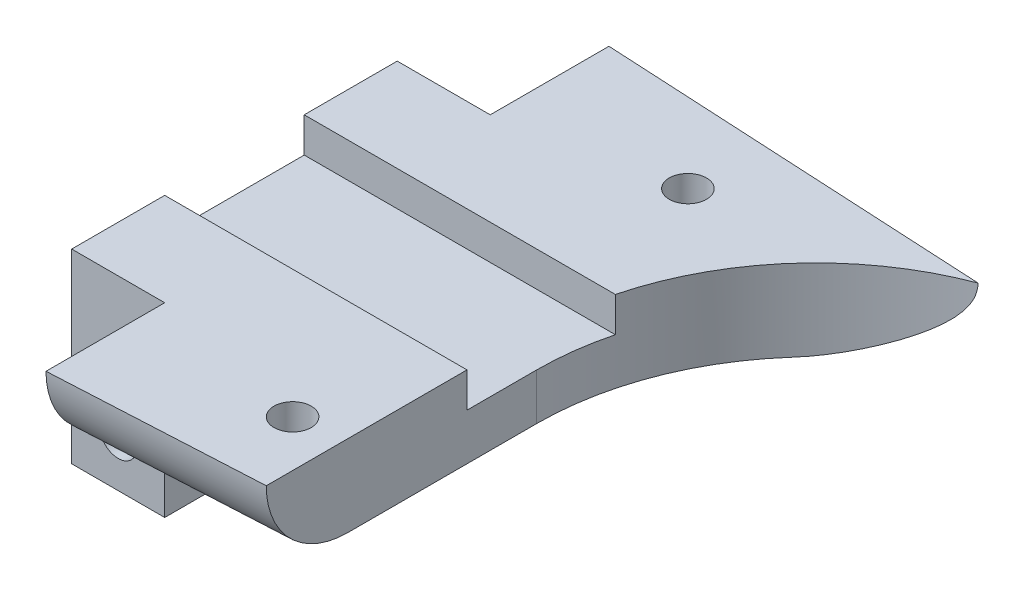
SolidWorks part; units mm, degrees
ref_plane "Front" through (0, 0, 0) normal (0, 0, 1) x (1, 0, 0)
ref_plane "Top" through (0, 0, 0) normal (0, 1, 0) x (1, 0, 0)
ref_plane "Right" through (0, 0, 0) normal (1, 0, 0) x (0, 0, -1)
sketch "Sketch1" plane through (0, 0, 0) normal (0, 1, 0) x (1, 0, 0)
  line L0 (0, 0) -> (38, 0) construction
  line L2 (0, 13) -> (17, 12.1053) construction
  line L3 (17, -12.1053) -> (33.7535, -11.2235)
  line L4 (0, -13) -> (17, -12.1053) construction
  line L5 (13, 0) -> (13, 7)
  line L7 (26, 0) -> (26, -11.6316)
  line L8 (17, 10) -> (17, 12.1053)
  line L9 (17, 12.1053) -> (33.7535, 11.2235)
  line L10 (17, -10) -> (17, -12.1053)
  line L13 (13, 7) -> (17, 7)
  line L14 (17, 7) -> (17, 10)
  line L15 (13, 0) -> (13, -7)
  line L16 (13, -7) -> (17, -7)
  line L17 (17, -7) -> (17, -10)
  circle A0 centre (0, 0) radius 13
  circle A1 centre (38, 0) radius 12
extrude "Boss-Extrude1" add sketch "Sketch1" against normal blind 3.5 contours A1 L9 L8 L14 L13 L5 L15 L16 L17 L10 L3 L7 region at (20.8147, 0, -0.7569)
sketch "Sketch2" plane through (0, 0, 0) normal (0, 1, 0) x (1, 0, 0)
  line L0 (0, 0) -> (24, 0) construction
  line L4 (24, 0) -> (24, 8.5) construction
  line L5 (24, 0) -> (24, -8.5) construction
  circle A0 centre (24, 8.5) radius 0.8
  circle A3 centre (24, -8.5) radius 0.8
extrude "Screw Holes" cut sketch "Sketch2" against normal through all
sketch "Sketch3" plane through (0, 0, 0) normal (0, 1, 0) x (1, 0, 0)
  line L1 (13, 7) -> (17, 7)
  line L2 (13, 7) -> (13, -7)
  line L3 (13, -7) -> (17, -7)
  line L4 (17, 7) -> (17, -7)
extrude "Boss-Extrude2" add sketch "Sketch3" against normal blind 8
sketch "Sketch4" plane through (0, 0, 0) normal (0, 1, 0) x (1, 0, 0)
  line L0 (13, 0) -> (13, 3)
  line L2 (13, 0) -> (13, -3)
  line L3 (13, -3) -> (26.381, -3)
  line L4 (26.381, -3) -> (26.381, 3)
  line L5 (26.381, 3) -> (13, 3)
extrude "Cut-Extrude1" cut sketch "Sketch4" against normal blind 1.5
sketch "Sketch5" plane through (0, 0, 0) normal (0, 0, 1) x (1, 0, 0)
  line L2 (15, 4) -> (15, -6) construction
  circle A0 centre (15, -6) radius 0.8
extrude "Cut-Extrude2" cut sketch "Sketch5" against normal through all from offset 13
fillet "Fillet1" radius 3.5 2 edges at (21.5, -3.5, 11.8684) (25.3767, -3.5, -11.6644)
